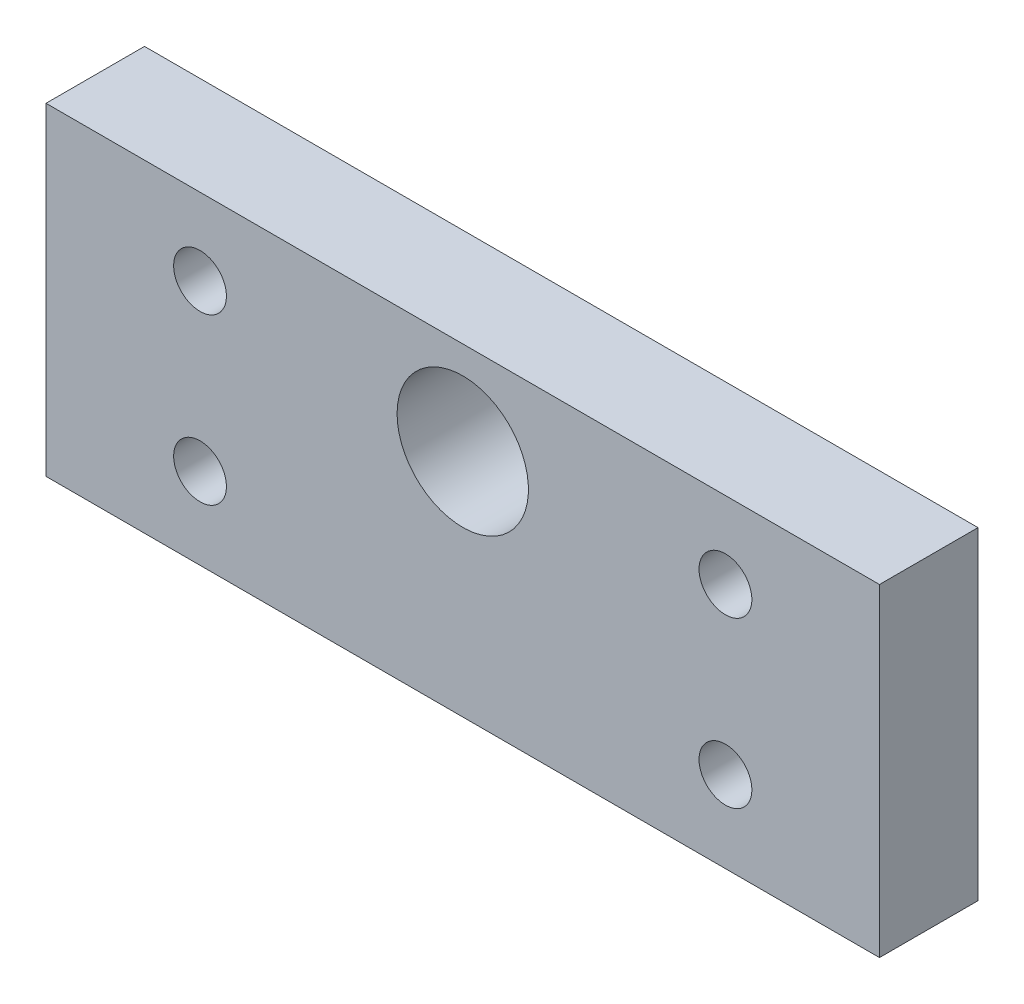
SolidWorks part; units mm, degrees
material "6061-T6 (SS)"
ref_plane "Front Plane" through (0, 0, 0) normal (0, 0, 1) x (1, 0, 0)
ref_plane "Top Plane" through (0, 0, 0) normal (0, 1, 0) x (1, 0, 0)
ref_plane "Right Plane" through (0, 0, 0) normal (1, 0, 0) x (0, 0, -1)
sketch "Sketch1" plane through (0, 0, 0) normal (0, 0, 1) x (1, 0, 0)
  line L0 (-40.2927, 31.242) -> (40.2927, 31.242)
  line L1 (-40.2927, 0) -> (-40.2927, 31.242)
  line L2 (40.2927, 0) -> (-40.2927, 0)
  line L3 (40.2927, 0) -> (40.2927, 31.242)
  line L6 (-40.2927, 0) -> (-40.2927, 31.75) construction
  circle A0 centre (0, 22.225) radius 6.35
  point P6 (0, 0)
  line B0 (63.5, 0) -> (63.5, 15.875)
  line B1 (63.5, 15.875) -> (38.4596, 15.875)
  line B2 (38.4596, 15.875) -> (47.625, 31.75)
  line B3 (47.625, 31.75) -> (16.0563, 31.75)
  line B4 (-40.2927, 31.75) -> (-31.1272, 15.875)
  line B5 (-31.1272, 15.875) -> (-63.5, 15.875)
  line B6 (-16.0563, 31.75) -> (-16.0563, 12.7)
  line B7 (16.0563, 12.7) -> (16.0563, 31.75)
  line B8 (-63.5, 47.625) -> (63.5, 47.625)
  line B9 (63.5, 47.625) -> (63.5, 15.875)
  line B10 (0, 47.625) -> (0, 0) construction
  line B11 (-38.4596, 15.875) -> (38.4596, 15.875) construction
  line B12 (-28.702, 36.957) -> (28.702, 36.957) construction
  line B13 (-25.4, 7.874) -> (25.4, 7.874) construction
  line B14 (-25.4, 7.874) -> (-25.4, 23.8125) construction
  line B15 (25.4, 7.874) -> (25.4, 23.8125) construction
  line B16 (-52.832, 23.8125) -> (52.832, 23.8125) construction
  circle B17 centre (0, 22.225) radius 18.669 construction
  dimension "D2" = 0.508
  dimension "D1" = 12.7
sketch_block_instance "dovetail pair-1"
sketch_block "dovetail pair" parameters "D8"=37.338, "D1"=60, "D2"=127, "D3"=6.35, "D4"=15.875, "D5"=31.75, "D6"=95.25, "D7"=19.05, "D9"=60, "D10"=31.75, "D11"=50.8, "D12"=23.876, "D13"=7.874, "D14"=10.668, "D15"=34.798, "D16"=21.082, "D17"=7.9375
extrude "Boss-Extrude1" add sketch "Sketch1" along normal blind 9.525
hole_wizard "CBORE for #10 Socket Head Cap Screw1" positions "Sketch2" profile "Sketch3" counterbore size "#10" standard "ANSI Inch" end condition up to next
sketch "Sketch2" plane through (0, 0, 0) normal (0, 0, 1) x (1, 0, 0)
  point P27 (25.4, 23.8125)
  point P29 (-25.4, 23.8125)
  point P31 (-25.4, 7.874)
  point P33 (25.4, 7.874)
sketch "Sketch3" plane through (25.4, 23.8125, 0) normal (1, 0, 0) x (0, 1, 0)
  line L0 (0, 0) -> (0, 9.525)
  line L1 (0, 9.525) -> (2.5527, 9.525)
  line L3 (2.5527, 9.525) -> (2.5527, 4.826)
  line L4 (4.7625, 4.826) -> (2.5527, 4.826)
  line L5 (4.7625, 4.826) -> (4.7625, 0.635)
  line L6 (4.7625, 0.635) -> (5.3975, 0)
  line L7 (5.3975, 0) -> (0, 0)
  line L8 (-4.7625, 0.635) -> (-5.3975, 0) construction
  line L11 (0, -6.35) -> (0, 107.95) construction
  dimension "Thru Hole Dia." = 5.1054
  dimension "Thru Hole Depth" = 9.525
  dimension "C'Bore Dia." = 9.525
  dimension "C'Bore Depth" = 4.826
  dimension "Near C'Sink Dia." = 10.795
  dimension "Near C'Sink Angle" = 90
ref_plane "center plane" through (0, 0, 0) normal (1, 0, 0) x (0, 0, -1)
equation "\"dovetail-angle\" = 60"
equation "\"dovetail-stock-width\" = 5"
equation "\"dovetail-stock-height\" = 1.25"
equation "\"dovetail-depth\" = 0.5 * \"dovetail-stock-height\""
equation "\"dovetail-throat-width\" = \"dovetail-stock-width\" - (2 * \"dovetail-depth\")"
equation "\"delta-x\" = 6"
equation "\"delta-y\" = 3"
equation "\"gib-thickness\" = 0.25"
equation "\"x-slide-length\" = \"dovetail-stock-width\" + \"delta-x\""
equation "\"y-slide-length\" = \"dovetail-stock-width\" + \"delta-y\""
equation "\"dog-point-diam\" = .149"
equation "\"dog-point-length\" = .067"
equation "\"dovetail-double-height\" = 2 * \"dovetail-depth\" + 0.5"
equation "\"acme-major-diam\" = .5"
equation "\"acme-pitch-diam\" = 0.45"
equation "\"acme-minor-diam\" = 0.4"
equation "\"acme-nut-od\" = 1.47"
equation "\"acme-nut-length\" = 1"
equation "\"acme-nut-trim-height\" = .75"
equation "\"screw-bearing-od\" = 0.5"
equation "\"screw-bearing-length\" = .375"
equation "\"screw-bearing-id\" = .3125"
equation "\"end-plate-thickness\" = \"screw-bearing-length\""
equation "\"screw-add-length\" = 2 * \"end-plate-thickness\" + 1 + 0.5"
equation "\"x-screw-length\" = \"x-slide-length\" + \"screw-add-length\""
equation "\"y-screw-length\" = \"y-slide-length\" + \"screw-add-length\""
equation "\"acme-nut-mount-hole-space-horz\" = 0.95"
equation "\"acme-nut-mount-hole-space-vert\" = 0.5 * \"acme-nut-length\""
equation "\"vise-hole-center-dist\" = 6.75"
equation "\"wiper_plate_clearance\" = .03"
equation "\"D1@Boss-Extrude1\"=\"screw-bearing-length\""
equation "\"D2@dovetail pair\"=\"dovetail-stock-width\""
equation "\"D1@dovetail pair\"=\"dovetail-angle\""
equation "\"D3@dovetail pair\"=\"gib-thickness\""
equation "\"D4@dovetail pair\"=\"dovetail-depth\""
equation "\"D5@dovetail pair\"=\"dovetail-stock-height\""
equation "\"D6@dovetail pair\"=\"dovetail-throat-width\""
equation "\"D10@dovetail pair\"=\"dovetail-stock-height\""
equation "\"D7@dovetail pair\"=\"acme-nut-trim-height\""
equation "\"D8@dovetail pair\"=\"acme-nut-od\""
equation "\"D9@dovetail pair\"=\"dovetail-angle\""
equation "\"D17@dovetail pair\"=\"dovetail-depth\"/2"
equation "\"D1@Sketch1\"=\"screw-bearing-od\""
equation "\"acme-nut-trim-width\" = 1.25"
equation "\"dial-width\" = 0.5"
equation "\"quarter-twenty-free-fit\" = .2667"
equation "\"acme_nut_clearance\" = .02"
equation "\"dovetail_male_clearance\" = .02"
equation "\"D2@Sketch1\"=\"dovetail_male_clearance\""
